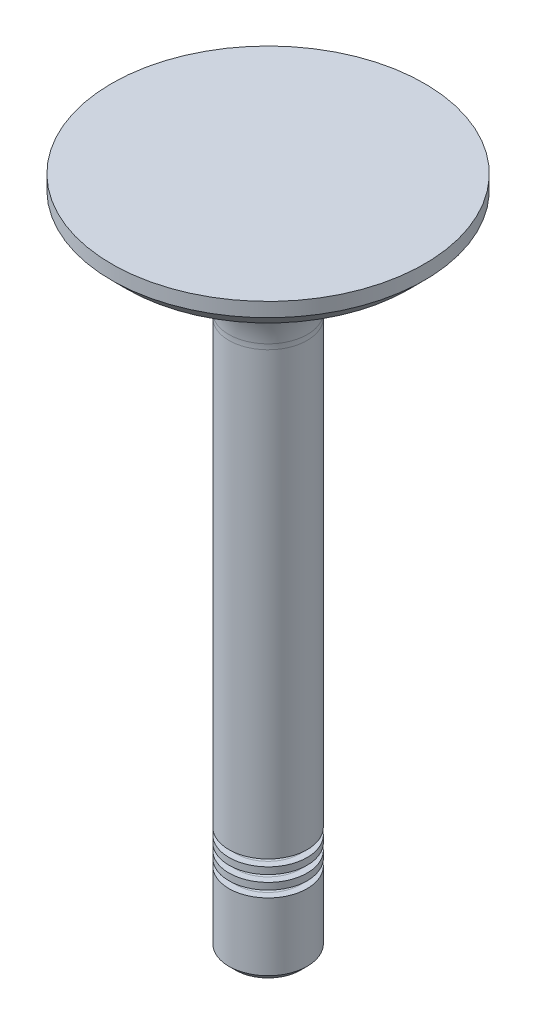
SolidWorks part; units mm, degrees
material "21-2N"
ref_plane "Front Plane" through (0, 0, 0) normal (0, 0, 1) x (1, 0, 0)
ref_plane "Top Plane" through (0, 0, 0) normal (0, 1, 0) x (1, 0, 0)
ref_plane "Right Plane" through (0, 0, 0) normal (1, 0, 0) x (0, 0, -1)
sketch "Sketch1" plane through (0, 0, 0) normal (0, 0, 1) x (1, 0, 0)
  line L0 (0, 105.7218) -> (0, 5.7218) construction
  line L1 (0, 105.7218) -> (-23.22, 105.7218)
  line L2 (-23.22, 105.7218) -> (-23.22, 103.6218)
  line L3 (-23.22, 103.6218) -> (-20.898, 101.2998)
  line L4 (0, 105.7218) -> (0, 5.7218)
  line L5 (-5.805, 87.4698) -> (-5.805, 5.7218)
  line L6 (-5.805, 5.7218) -> (0, 5.7218)
  arc A0 (-20.898, 101.2998) -> (-5.805, 87.4698) centre (-20.2665, 86.8383) cw
  dimension "D2" = 23.22
  dimension "D3" = 2.1
  dimension "D4" = 45
  dimension "D1" = 5.805
  dimension "D6" = 100
  dimension "D5" = 2.322
  dimension "D8" = 16.152
revolve "Revolve1" add sketch "Sketch1" angle 360 about L0
fillet "Fillet1" radius 10 1 edges at (-5.805, 87.4698, 0)
chamfer "Chamfer1" distance 1 angle 45 1 edges at (-5.805, 5.7218, 0)
sketch "Sketch2" plane through (0, 0, 0) normal (1, 0, 0) x (0, 0, -1)
  line L2 (-6.805, 19.7218) -> (-4.805, 19.7218)
  line L3 (-6.805, 18.7218) -> (-4.805, 18.7218)
  line L4 (0, 6.7218) -> (0, 87.9734) construction
  line L5 (5.805, 6.7218) -> (-5.805, 6.7218) construction
  line L6 (5.8358, 87.9734) -> (-5.8358, 87.9734) construction
  line L7 (-6.805, 18.7218) -> (-6.805, 19.7218)
  line L8 (-6.805, 16.7218) -> (-4.805, 16.7218)
  line L9 (-6.805, 16.7218) -> (-6.805, 17.7218)
  line L10 (-6.805, 17.7218) -> (-4.805, 17.7218)
  line L12 (-6.805, 21.7218) -> (-4.805, 21.7218)
  line L13 (-6.805, 20.7218) -> (-4.805, 20.7218)
  line L14 (-6.805, 20.7218) -> (-6.805, 21.7218)
  arc A1 (-4.805, 16.7218) -> (-4.805, 17.7218) centre (-4.805, 17.2218) ccw
  arc A2 (-4.805, 18.7218) -> (-4.805, 19.7218) centre (-4.805, 19.2218) ccw
  arc A3 (-4.805, 20.7218) -> (-4.805, 21.7218) centre (-4.805, 21.2218) ccw
  point P10 (-5.805, 17.2218)
  dimension "D1" = 10
  dimension "D2" = 1
  dimension "D3" = 3
revolve "Cut-Revolve1" cut sketch "Sketch2" angle 360 about L4
equation "\"Valve Diameter\"= 46.44mm"
equation "\"Seat Angle Beta\"= 45deg"
equation "\"Seat Diameter\"= 41.796mm"
equation "\"Stem Diameter\"= 11.61mm"
equation "\"Seat Width\"= 2.322mm"
equation "\"Max Lift\"= 16.152mm"
equation "\"Overall Length\"= 100mm"
equation "\"Head Thickness\"= 2.1mm"
equation "\"D2@Sketch1\"=\"Valve Diameter\"/2"
equation "\"D3@Sketch1\"=\"Head Thickness\""
equation "\"D4@Sketch1\"=\"Seat Angle Beta\""
equation "\"D1@Sketch1\"=\"Stem Diameter\"/2"
equation "\"D6@Sketch1\"=\"Overall Length\""
equation "\"D5@Sketch1\"=\"Seat Width\""
equation "\"D8@Sketch1\"=\"Max Lift\""
